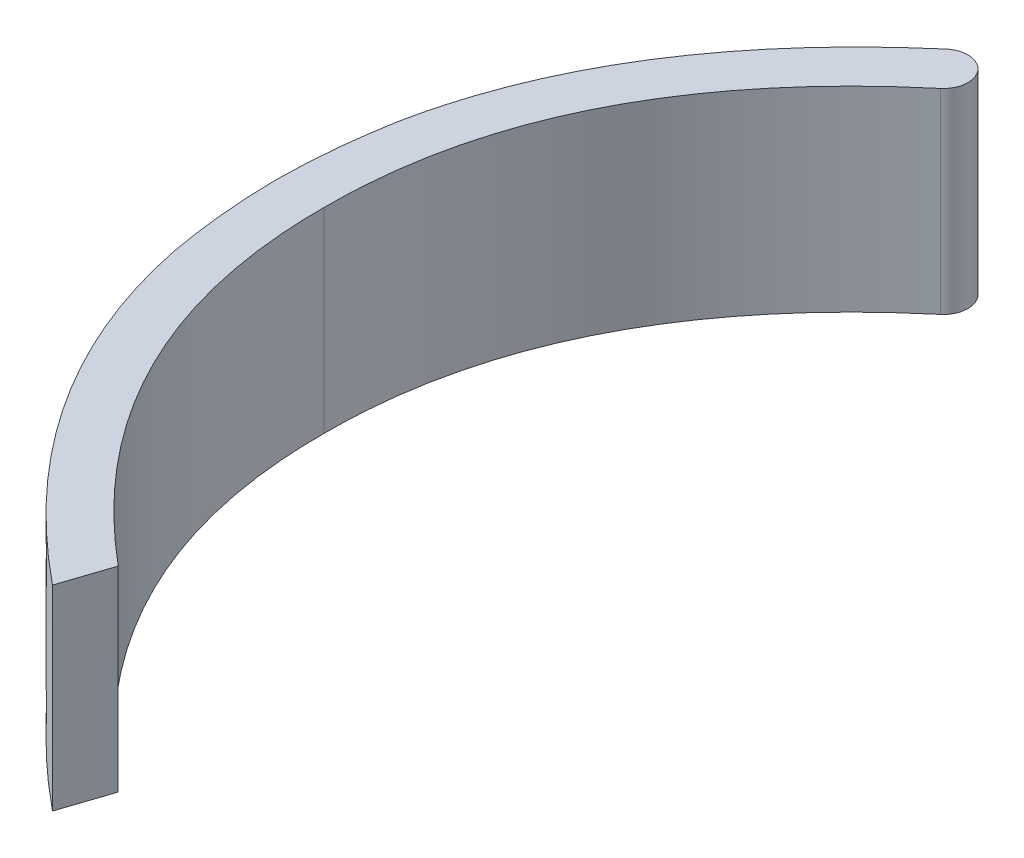
SolidWorks part; units mm, degrees
ref_plane "前视基准面" through (0, 0, 0) normal (0, 0, 1) x (1, 0, 0)
ref_plane "上视基准面" through (0, 0, 0) normal (0, 1, 0) x (1, 0, 0)
ref_plane "右视基准面" through (0, 0, 0) normal (1, 0, 0) x (0, 0, -1)
sketch "草图1" plane through (0, 0, 0) normal (0, 1, 0) x (1, 0, 0)
  line L4 (0, 17.5) -> (0, -17.5)
  line L5 (0, -17.5) -> (-5.05, -12.45)
  line L6 (-17.5, 0) -> (-9.9169, 7.5831)
  line L7 (0, 17.5) -> (-5.05, 12.45)
  line L9 (0, 17.5) -> (-1.4142, 18.9142)
  line L10 (-1.4142, -18.9142) -> (-0.7071, -16.7929)
  line L11 (0, -17.5) -> (-1.4142, -18.9142)
  line L12 (-5.05, 12.45) -> (0, 17.5)
  circle A2 centre (0, 0) radius 17.5
  spline S0 degree 2 poles (-1.4142, 18.9142) (-13.2682, 9.2904) (-10.75, -4.6079) knots 0 0 0 1 1 1
  spline S1 degree 2 poles (-1.4142, -18.9142) (-13.2682, -9.2904) (-10.75, 4.6079) knots 0 0 0 1 1 1
  spline S2 degree 2 poles (0, -17.5) (-11.3377, -8.5857) (-8.75, 4.6079) knots 0 0 0 1 1 1
  spline S3 degree 2 poles (0, 17.5) (-11.3377, 8.5857) (-8.75, -4.6079) knots 0 0 0 1 1 1
  point P10 (-8.75, 8.75)
  dimension "D5" = 35
  dimension "D3" = 2
  dimension "D4" = 2
extrude "凸台-拉伸1" add sketch "草图1" along normal blind 8 contours S3 A2 S0 S1 L10 S2 | L9 S0 A2 | S1 L10 A2 region at (-1.6163, 0, -17.9006) region at (-2.945, 0, -15.3965) region at (-1.9229, 0, 17.8766)
fillet "圆角2" radius 1 2 edges at (-1.4142, 4, -18.9142) (0, 4, -17.5)
